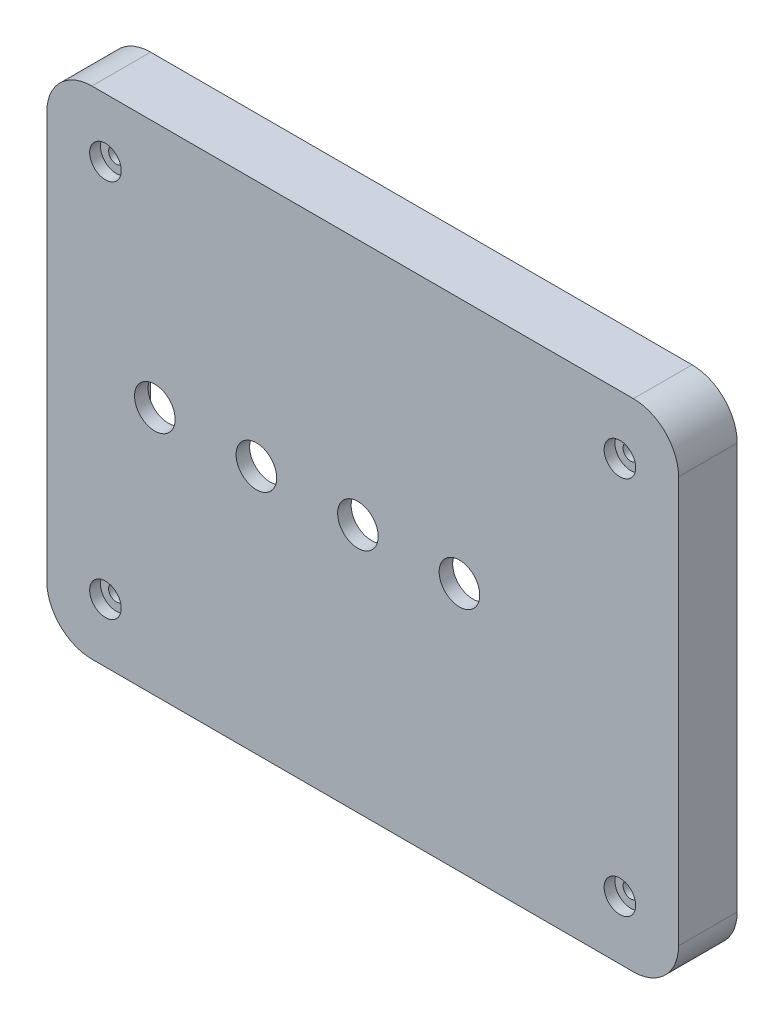
SolidWorks part; units mm, degrees
ref_plane "Front Plane" through (0, 0, 0) normal (0, 0, 1) x (1, 0, 0)
ref_plane "Top Plane" through (0, 0, 0) normal (0, 1, 0) x (1, 0, 0)
ref_plane "Right Plane" through (0, 0, 0) normal (1, 0, 0) x (0, 0, -1)
sketch "Sketch1" plane through (0, 0, 0) normal (0, 0, 1) x (1, 0, 0)
  line L0 (128.6764, 77.0848) -> (128.6764, -12.9152) construction
  line L1 (118.6764, -22.9152) -> (-1.3236, -22.9152) construction
  line L2 (-11.3236, -12.9152) -> (-11.3236, 77.0848) construction
  line L3 (-1.3236, 87.0848) -> (118.6764, 87.0848) construction
  line L4 (128.6764, 77.0848) -> (128.6764, -12.9152)
  line L5 (118.6764, -22.9152) -> (-1.3236, -22.9152)
  line L6 (-11.3236, -12.9152) -> (-11.3236, 77.0848)
  line L7 (-1.3236, 87.0848) -> (118.6764, 87.0848)
  arc A0 (128.6764, 77.0848) -> (118.6764, 87.0848) centre (118.6764, 77.0848) ccw construction
  arc A1 (118.6764, -22.9152) -> (128.6764, -12.9152) centre (118.6764, -12.9152) ccw construction
  arc A2 (-11.3236, -12.9152) -> (-1.3236, -22.9152) centre (-1.3236, -12.9152) ccw construction
  arc A3 (-1.3236, 87.0848) -> (-11.3236, 77.0848) centre (-1.3236, 77.0848) ccw construction
  arc A4 (128.6764, 77.0848) -> (118.6764, 87.0848) centre (118.6764, 77.0848) ccw
  arc A5 (118.6764, -22.9152) -> (128.6764, -12.9152) centre (118.6764, -12.9152) ccw
  arc A6 (-11.3236, -12.9152) -> (-1.3236, -22.9152) centre (-1.3236, -12.9152) ccw
  arc A7 (-1.3236, 87.0848) -> (-11.3236, 77.0848) centre (-1.3236, 77.0848) ccw
extrude "Boss-Extrude1" add sketch "Sketch1" along normal offset from surface (13 mm away) 6 offset beyond the face yes
sketch "Sketch2" plane through (0, 0, 0) normal (0, 0, -1) x (-1, 0, 0)
  line L0 (-12.54, 77.0848) -> (-87.79, 77.0848) construction
  line L1 (1.3236, 12.5385) -> (1.3236, 57.31) construction
  line L3 (-109.6764, -12.9152) -> (-7.6764, -12.9152) construction
  line L4 (-118.6764, 68.0848) -> (-118.6764, -3.9152) construction
  line L5 (-12.54, 77.0848) -> (-87.79, 77.0848)
  line L6 (1.3236, 12.5385) -> (1.3236, 70.5848)
  line L8 (-109.6764, -12.9152) -> (-7.6764, -12.9152)
  line L9 (-118.6764, 68.0848) -> (-118.6764, -3.9152)
  line L10 (-12.54, 77.0848) -> (-5.1764, 77.0848)
  line L11 (-87.79, 77.0848) -> (-109.6764, 77.0848)
  line L12 (1.3236, 12.5385) -> (1.3236, -6.9152)
  line L20 (-1.6764, 70.5848) -> (1.3236, 70.5848)
  line L21 (-5.1764, 74.0848) -> (-5.1764, 77.0848)
  line L33 (-1.6764, -6.9152) -> (1.3236, -6.9152)
  arc A19 (-5.1764, 74.0848) -> (-1.6764, 70.5848) centre (-1.6764, 74.0848) ccw
  arc A24 (-115.6764, 71.0848) -> (-118.6764, 68.0848) centre (-115.6764, 68.0848) ccw construction
  arc A25 (-115.6764, 71.0848) -> (-112.6764, 74.0848) centre (-115.6764, 74.0848) ccw construction
  arc A26 (-109.6764, 77.0848) -> (-112.6764, 74.0848) centre (-109.6764, 74.0848) ccw construction
  arc A27 (-115.6764, 71.0848) -> (-118.6764, 68.0848) centre (-115.6764, 68.0848) ccw
  arc A36 (-115.6764, 71.0848) -> (-112.6764, 74.0848) centre (-115.6764, 74.0848) ccw
  arc A37 (-109.6764, 77.0848) -> (-112.6764, 74.0848) centre (-109.6764, 74.0848) ccw
  arc A38 (-1.6764, -6.9152) -> (-4.6764, -9.9152) centre (-1.6764, -9.9152) ccw
  arc A39 (-7.6764, -12.9152) -> (-4.6764, -9.9152) centre (-7.6764, -9.9152) ccw construction
  arc A40 (-7.6764, -12.9152) -> (-4.6764, -9.9152) centre (-7.6764, -9.9152) ccw
  arc A41 (-118.6764, -3.9152) -> (-115.6764, -6.9152) centre (-115.6764, -3.9152) ccw construction
  arc A42 (-112.6764, -9.9152) -> (-115.6764, -6.9152) centre (-115.6764, -9.9152) ccw construction
  arc A43 (-112.6764, -9.9152) -> (-109.6764, -12.9152) centre (-109.6764, -9.9152) ccw construction
  arc A44 (-118.6764, -3.9152) -> (-115.6764, -6.9152) centre (-115.6764, -3.9152) ccw
  arc A45 (-112.6764, -9.9152) -> (-115.6764, -6.9152) centre (-115.6764, -9.9152) ccw
  arc A46 (-112.6764, -9.9152) -> (-109.6764, -12.9152) centre (-109.6764, -9.9152) ccw
  dimension "D1" = 7
extrude "Cut-Extrude1" cut sketch "Sketch2" against normal offset from surface (10 mm away) 3 up to face at (58.6764, 32.0848, 13)
hole_wizard "CBORE for M3 Pan Head Screw1" positions "Sketch3" profile "Sketch4" counterbore size "M3" standard "ISO"
sketch "Sketch3" plane through (0, 0, 13) normal (0, 0, 1) x (1, 0, 0)
  point P0 (1.6764, -9.9152)
  point P3 (115.6764, -9.9152)
  point P6 (115.6764, 74.0848)
  point P9 (1.6764, 74.0848)
sketch "Sketch4" plane through (1.6764, -9.9152, 13) normal (1, 0, 0) x (0, -1, 0)
  line L0 (0, 0) -> (0, 16.0215)
  line L1 (0, 16.0215) -> (1.7, 15)
  line L2 (1.7, 15) -> (1.7, 2.4)
  line L3 (1.7, 2.4) -> (3.5, 2.4)
  line L4 (3.5, 2.4) -> (3.5, 0)
  line L5 (3.5, 0) -> (0, 0)
  line L10 (0, 16.0215) -> (-1.7, 15) construction
  line L11 (0, -6.35) -> (0, 107.95) construction
  dimension "Hole Dia." = 3.4
  dimension "Hole Depth" = 15
  dimension "C'Bore Dia." = 7
  dimension "C'Bore Depth" = 2.4
  dimension "Drill Angle" = 118
fillet "Fillet1" radius 3 3 edges at (-1.3236, 70.5848, 5) (5.1764, 77.0848, 5) (-1.3236, -6.9152, 5)
sketch "Sketch5" plane through (0, 0, 13) normal (0, 0, 1) x (1, 0, 0)
  line L0 (12.6214, 32.3367) -> (99.9994, 32.3367) construction
  line L1 (99.9994, 0) -> (99.9994, 70) construction
  line L9 (12.6214, 33.064) -> (12.6214, 29) construction
  line L10 (11.6054, 33.064) -> (13.6374, 33.064) construction
  line L11 (13.6374, 29) -> (11.6054, 29) construction
  line L12 (60.1722, 44.4436) -> (58.5466, 44.4436) construction
  line L13 (60.1722, 45.4025) -> (60.1722, 43.4848) construction
  line L14 (58.5466, 45.4025) -> (58.5466, 43.4848) construction
  line L15 (59.3594, 44.4436) -> (59.3594, 47.8324) construction
  circle A0 centre (12.6214, 32.3367) radius 4.5
  circle A1 centre (35.1214, 32.3367) radius 4.5
  circle A2 centre (57.6214, 32.3367) radius 4.5
  circle A3 centre (80.1214, 32.3367) radius 4.5
  dimension "D1" = 9
  dimension "D2" = 9
  dimension "D3" = 9
  dimension "D4" = 9
  dimension "D5" = 22.5
  dimension "D6" = 22.5
  dimension "D7" = 22.5
extrude "Cut-Extrude2" cut sketch "Sketch5" against normal through all
equation "\"D6@Sketch5\"=\"D5@Sketch5\""
equation "\"D7@Sketch5\"=\"D5@Sketch5\""
